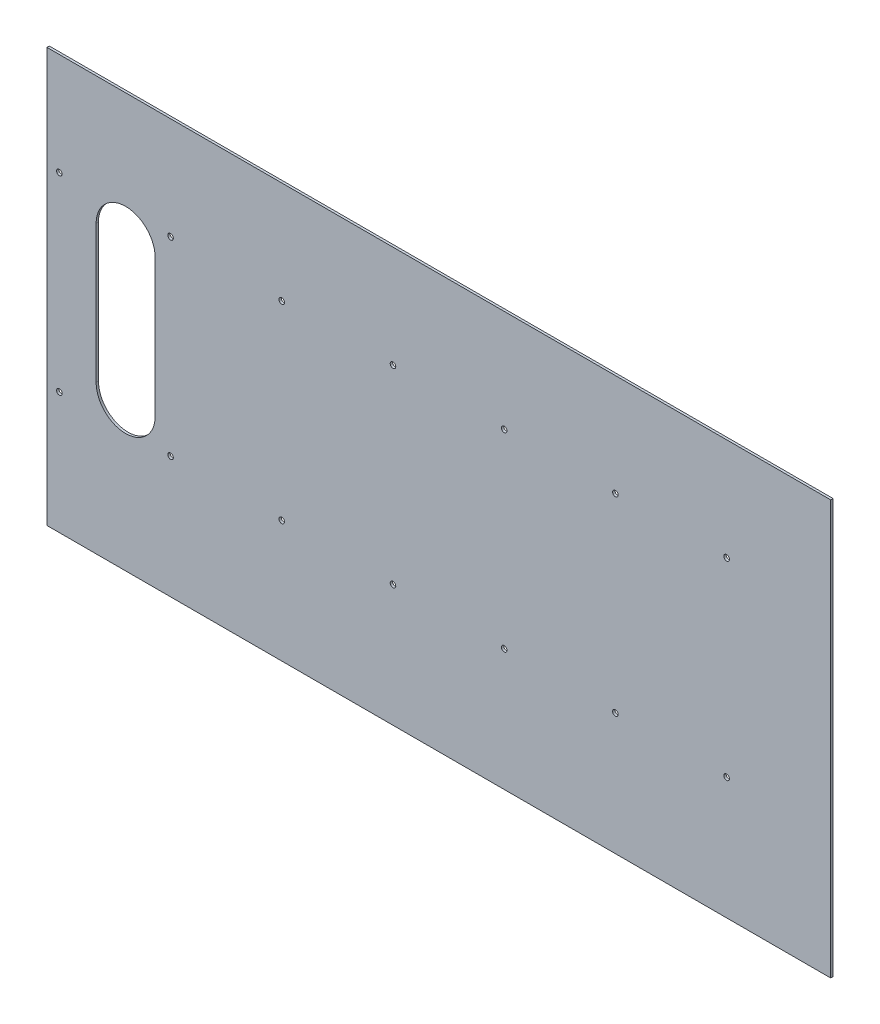
SolidWorks part; units mm, degrees
material "5052-H32"
ref_plane "Front Plane" through (0, 0, 0) normal (0, 0, 1) x (1, 0, 0)
ref_plane "Top Plane" through (0, 0, 0) normal (0, 1, 0) x (1, 0, 0)
ref_plane "Right Plane" through (0, 0, 0) normal (1, 0, 0) x (0, 0, -1)
sketch "Sketch1" plane through (0, 0, 0) normal (0, 0, 1) x (1, 0, 0)
  line L0 (-425.1425, -1.5189) -> (80.8575, -1.5189) construction
  line L1 (-425.1425, -65.0189) -> (80.8575, -65.0189)
  line L2 (-425.1425, -65.0189) -> (-425.1425, 202.3189)
  line L3 (-425.1425, 202.3189) -> (80.8575, 202.3189)
  line L4 (80.8575, -65.0189) -> (80.8575, 202.3189)
  line L5 (-172.1425, 202.3189) -> (-172.1425, -65.0189) construction
  line L6 (-425.1425, 68.65) -> (80.8575, 68.65) construction
  line L7 (80.8575, 151.5189) -> (-425.1425, 151.5189) construction
  line L8 (80.8575, -1.5189) -> (80.8575, 0) construction
  point P112 (-172.1425, 68.65)
  dimension "D1" = 506
  dimension "D2" = 63.5
  dimension "D3" = 50.8
base flange "Base-Flange1" sketch "Sketch1" thickness 1.5189 reverse thickness direction yes parameters "D1"=1.905
sketch "Sketch6" plane through (0, 0, 1.5189) normal (0, 0, 1) x (1, 0, 0)
  line L0 (-374.3425, 30.8689) -> (-374.3425, 119.7689) construction
  line L1 (-393.3925, 30.8689) -> (-393.3925, 119.7689)
  line L2 (-355.2925, 30.8689) -> (-355.2925, 119.7689)
  line L3 (80.8575, 202.3189) -> (-425.1425, 202.3189) construction
  line L4 (-425.1425, 202.3189) -> (-425.1425, -65.0189) construction
  arc A0 (-393.3925, 30.8689) -> (-355.2925, 30.8689) centre (-374.3425, 30.8689) ccw
  arc A1 (-355.2925, 119.7689) -> (-393.3925, 119.7689) centre (-374.3425, 119.7689) ccw
  point P2 (-374.3425, 75.3189)
  dimension "D2" = 38.1
  dimension "D3" = 63.5
  dimension "D1" = 88.9
  dimension "D4" = 50.8
extrude "Cut-Extrude1" cut sketch "Sketch6" against normal blind 2.54
hole_wizard "M3 Clearance Hole1" positions "Sketch8" profile "Sketch7" hole size "M3" standard "ANSI Metric"
sketch "Sketch8" plane through (0, 0, 1.5189) normal (0, 0, 1) x (1, 0, 0)
  line L0 (-425.1425, 75) -> (80.8575, 75) construction
  line L1 (-425.1425, 202.3189) -> (-425.1425, -65.0189) construction
  line L5 (-417.1425, 136.3375) -> (-345.3417, 136.3375) construction
  line L6 (80.8575, -65.0189) -> (80.8575, 202.3189) construction
  line L7 (-425.1425, 68.65) -> (80.8575, 68.65) construction
  point P0 (-417.1425, 136.3375)
  point P2 (-417.1425, 13.6625)
  point P19 (-345.3417, 136.3375)
  point P20 (-345.3417, 13.6625)
  point P21 (-273.5408, 136.3375)
  point P22 (-273.5408, 13.6625)
  point P23 (-201.74, 136.3375)
  point P24 (-201.74, 13.6625)
  point P25 (-129.9392, 136.3375)
  point P26 (-129.9392, 13.6625)
  point P27 (-58.1383, 136.3375)
  point P28 (-58.1383, 13.6625)
  point P29 (13.6625, 136.3375)
  point P30 (13.6625, 13.6625)
  dimension "D1" = 122.675
  dimension "D2" = 8
  dimension "D4" = 71.8008
  dimension "D5" = 6.35
  dimension "D3" = 7
sketch "Sketch7" plane through (-417.1425, 136.3375, 1.5189) normal (1, 0, 0) x (0, -1, 0)
  line L0 (0, 0) -> (0, 13.0195)
  line L1 (0, 13.0195) -> (1.8, 11.938)
  line L2 (1.8, 11.938) -> (1.8, 0)
  line L5 (1.8, 0) -> (0, 0)
  line L10 (0, 13.0195) -> (-1.8, 11.938) construction
  line L11 (0, -6.35) -> (0, 107.95) construction
  dimension "Hole Dia." = 3.6
  dimension "Hole Depth" = 11.938
  dimension "Drill Angle" = 118
sketch "Bend-Lines1" [suppressed] plane through (0, 0, 0) normal (0, 1, 0) x (1, 0, 0)
sketch "Bounding-Box1" [suppressed] plane through (0, 0, 0) normal (0, 1, 0) x (1, 0, 0)
sheet metal parameters "Sheet-Metal1" thickness 1.5189 parameters "D1"=1.905
flat pattern "Flat-Pattern1" [suppressed]
sketch "Bend-Lines2" plane through (0, 0, 0) normal (0, 1, 0) x (1, 0, 0)
sketch3d "Bounding-Box2" [suppressed]
  line L0 (-425, -48.9877, 0) -> (80.715, -48.9877, 0) construction
  line L1 (-425, 200.6275, 0) -> (80.715, 200.6275, 0) construction
  line L2 (-425, -48.9877, 0) -> (-425, 200.6275, 0) construction
  line L3 (80.715, -48.9877, 0) -> (80.715, 200.6275, 0) construction
sheet metal parameters "Sheet-Metal2" thickness 1.5189 parameters "D1"=1.905
flat pattern "Flat-Pattern1"
sketch "Bend-Lines2" plane through (0, 0, 0) normal (0, 1, 0) x (1, 0, 0)
sketch3d "Bounding-Box2" [suppressed]
  line L0 (425.1425, -65.0189, 0) -> (-80.8575, -65.0189, 0) construction
  line L1 (425.1425, 202.3189, 0) -> (-80.8575, 202.3189, 0) construction
  line L2 (425.1425, -65.0189, 0) -> (425.1425, 202.3189, 0) construction
  line L3 (-80.8575, -65.0189, 0) -> (-80.8575, 202.3189, 0) construction
sheet metal parameters "Sheet-Metal3" thickness 1.5189 parameters "D1"=1.905
flat pattern "Flat-Pattern1"
sketch "Bend-Lines2" plane through (0, 0, 0) normal (0, 1, 0) x (1, 0, 0)
sketch3d "Bounding-Box2" [suppressed]
  line L0 (425.1425, -65.0189, 0) -> (-80.8575, -65.0189, 0) construction
  line L1 (425.1425, 202.3189, 0) -> (-80.8575, 202.3189, 0) construction
  line L2 (425.1425, -65.0189, 0) -> (425.1425, 202.3189, 0) construction
  line L3 (-80.8575, -65.0189, 0) -> (-80.8575, 202.3189, 0) construction
